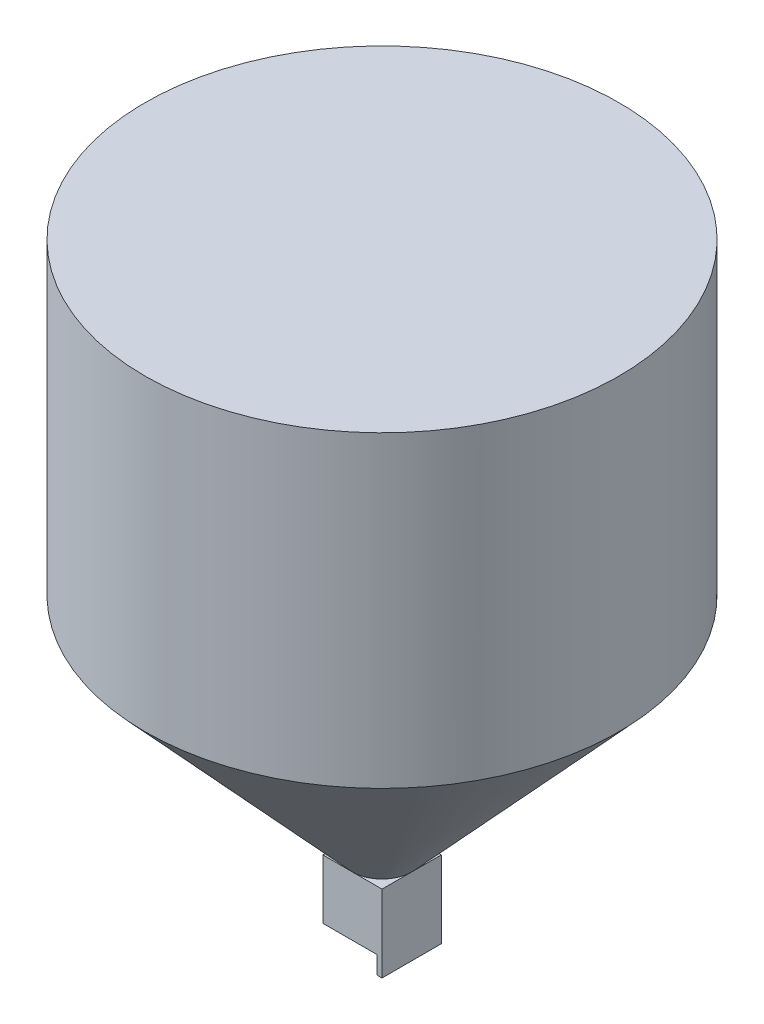
SolidWorks part; units mm, degrees
ref_plane "Alzado" through (0, 0, 0) normal (0, 0, 1) x (1, 0, 0)
ref_plane "Planta" through (0, 0, 0) normal (0, 1, 0) x (1, 0, 0)
ref_plane "Vista lateral" through (0, 0, 0) normal (1, 0, 0) x (0, 0, -1)
sketch "Croquis1" plane through (0, 0, 0) normal (0, 1, 0) x (1, 0, 0)
  circle A0 centre (0, 0) radius 400
  dimension "D1" = 800
ref_plane "Plano1" through (0, -900, 0) normal (0, 1, 0) x (1, 0, 0)
extrude "Saliente-Extruir1" add sketch "Croquis1" against normal blind 520 contours A0
sketch "Croquis2" plane through (0, -520, 0) normal (0, -1, 0) x (1, 0, 0)
  circle A0 centre (0, 0) radius 400
  dimension "D1" = 800
sketch "Croquis3" plane through (0, -900, 0) normal (0, 1, 0) x (1, 0, 0)
  circle A0 centre (0, 0) radius 50
  dimension "D1" = 100
loft "Recubrir1" add profiles "Croquis3", "Croquis2" connector at (-49.9253, -900, 2.7318) connector at (-399.2107, -520, 25.1162)
sketch "Croquis4" plane through (0, -900, 0) normal (0, -1, 0) x (1, 0, 0)
  line L1 (-50, -50) -> (50, -50)
  line L2 (-50, -50) -> (-50, 50)
  line L3 (-50, 50) -> (50, 50)
  line L4 (50, -50) -> (50, 50)
extrude "Saliente-Extruir2" add sketch "Croquis4" along normal blind 100
sketch "Croquis5" plane through (0, -1000, 0) normal (0, -1, 0) x (1, 0, 0)
  line L0 (50, 50) -> (-50, 50) construction
  line L1 (50, -50) -> (41.2943, -50)
  line L2 (50, -50) -> (50, 50)
  line L3 (50, 50) -> (41.2943, 50)
  line L4 (41.2943, -50) -> (41.2943, 50)
extrude "Saliente-Extruir3" add sketch "Croquis5" along normal blind 30
